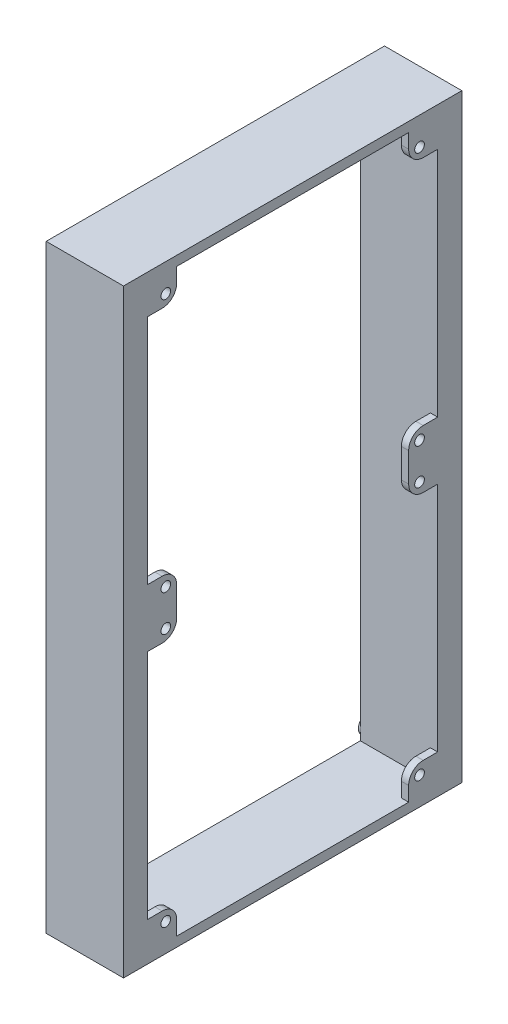
SolidWorks part; units mm, degrees
ref_plane "Front Plane" through (0, 0, 0) normal (1, 0, 0) x (0, 1, 0)
ref_plane "Top Plane" through (0, 0, 0) normal (0, 0, 1) x (0, 1, 0)
ref_plane "Right Plane" through (0, 0, 0) normal (0, 1, 0) x (-1, 0, 0)
sketch "Sketch1" plane through (0, 0, 0) normal (1, 0, 0) x (0, 1, 0)
  line L0 (0, 60) -> (0, -60) construction
  line L1 (-120, -60) -> (120, -60)
  line L2 (-120, -60) -> (-120, 60)
  line L3 (-120, 60) -> (120, 60)
  line L4 (120, -60) -> (120, 60)
  line L5 (-120, -60) -> (120, 60) construction
  line L6 (-120, 60) -> (120, -60) construction
  line L7 (0, 60) -> (0, -60.0055) construction
  line L8 (-120, -60) -> (0, 60) construction
  line L9 (-12, 60) -> (0, 60)
  line L10 (-120, 48) -> (-114, 48)
  line L11 (-120, 48) -> (-120, 60)
  line L12 (-120, 60) -> (-108, 60)
  line L13 (-108, 54) -> (-108, 60)
  line L14 (-12, 60) -> (-12, 54)
  line L15 (-6, 48) -> (0, 48)
  line L16 (0, 60) -> (0, 48)
  line L17 (0, -48) -> (0, -60)
  line L18 (0, -48) -> (-6, -48)
  line L19 (-12, -54) -> (-12, -60)
  line L20 (0, -60) -> (-12, -60)
  line L21 (-108, -60) -> (-120, -60)
  line L22 (-108, -60) -> (-108, -54)
  line L23 (-114, -48) -> (-120, -48)
  line L24 (-120, -60) -> (-120, -48)
  line L25 (0, 48) -> (0, 60)
  line L26 (0, 48) -> (6, 48)
  line L27 (12, 54) -> (12, 60)
  line L28 (0, 60) -> (12, 60)
  line L29 (12, -60) -> (0, -60)
  line L30 (0, -60) -> (0, -48)
  line L31 (6, -48) -> (0, -48)
  line L32 (12, -60) -> (12, -54)
  line L33 (120, -48) -> (120, -60)
  line L34 (120, -60) -> (108, -60)
  line L35 (108, -54) -> (108, -60)
  line L36 (120, -48) -> (114, -48)
  line L37 (108, 60) -> (120, 60)
  line L38 (120, 60) -> (120, 48)
  line L39 (114, 48) -> (120, 48)
  line L40 (108, 60) -> (108, 54)
  line L59 (-124, 70) -> (124, 70)
  line L60 (-124, 70) -> (-124, -70)
  line L61 (-124, -70) -> (124, -70)
  line L62 (124, 70) -> (124, -70)
  line L63 (-124, 70) -> (124, -70) construction
  line L64 (-124, -70) -> (124, 70) construction
  circle A0 centre (-112.5, 52.5) radius 2
  arc A1 (-114, 48) -> (-108, 54) centre (-114, 54) ccw
  arc A2 (-12, 54) -> (-6, 48) centre (-6, 54) ccw
  circle A3 centre (-7.5, 52.5) radius 2
  arc A4 (-6, -48) -> (-12, -54) centre (-6, -54) ccw
  circle A5 centre (-7.5, -52.5) radius 2
  arc A6 (-108, -54) -> (-114, -48) centre (-114, -54) ccw
  circle A7 centre (-112.5, -52.5) radius 2
  arc A8 (6, 48) -> (12, 54) centre (6, 54) ccw
  circle A9 centre (7.5, 52.5) radius 2
  circle A10 centre (7.5, -52.5) radius 2
  arc A11 (12, -54) -> (6, -48) centre (6, -54) ccw
  arc A12 (114, -48) -> (108, -54) centre (114, -54) ccw
  circle A13 centre (112.5, -52.5) radius 2
  arc A14 (108, 54) -> (114, 48) centre (114, 54) ccw
  circle A15 centre (112.5, 52.5) radius 2
  point P0 (0, 0)
  point P12 (0, 0)
  point P16 (-60, 0)
  point P18 (-117, 48)
  point P19 (-108, 57)
  point P22 (-108, 48)
  point P24 (0, 0)
  dimension "D3" = 4
  dimension "D5" = 105
  dimension "D8" = 6
  dimension "D1" = 240
  dimension "D2" = 120
  dimension "D4" = 7.5
  dimension "D6" = 120
  dimension "D7" = 12
  dimension "D9" = 120
  dimension "D10" = 4
  dimension "D11" = 2
  dimension "D12" = 248
  dimension "D13" = 140
extrude "Boss-Extrude2" add sketch "Sketch1" along normal blind 3 contours L10 A1 L13 L3 L2 A0 | L62 L59 L60 L61 L4 L1 L2 L3 | L14 A2 L15 L16 L3 A3 | L26 A8 L27 L3 L16 A9 | L40 A14 L39 L4 L3 A15 | L36 A12 L35 L1 L4 A13 | L32 A11 L31 L17 L1 A10 | L18 A4 L19 L1 L17 A5 | L22 A6 L23 L2 L1 A7 region at (0, -114.4434, -54.4434) region at (0, -5.5566, -54.4434) region at (0, -114.4434, 54.4434) region at (0, 5.5566, -54.4434) region at (0, 114.4434, -54.4434) region at (0, -5.5566, 54.4434) region at (0, 5.5566, 54.4434) region at (0, 114.4434, 54.4434) region at (0, 0, 67.1521)
extrude "Boss-Extrude5" add sketch "Sketch1<6>" against normal blind 29 contours L62 L59 L60 L61 L4 L1 L2 L3 region at (0, 0, 67.1521)
sketch "Sketch1<6>" plane through (0, 0, 0) normal (1, 0, 0) x (0, 1, 0) same geometry as "Sketch1"
sketch "Sketch14" plane through (-29, 0, 0) normal (-1, 0, 0) x (0, -1, 0)
  line L1 (0, 0) -> (-50000, 0) construction
  line L2 (-124, 70) -> (-124, -70) construction
  line L3 (0, 0) -> (0, -50000) construction
  line L4 (120, -60) -> (-120, -60) construction
  line L5 (124, 70) -> (-124, 70) construction
  line L6 (-123, 69) -> (123, 69)
  line L7 (-123, 69) -> (-123, -69)
  line L8 (-123, -69) -> (123, -69)
  line L9 (123, 69) -> (123, -69)
  line L10 (-122.6, 68.6) -> (122.6, 68.6)
  line L11 (122.6, 68.6) -> (122.6, -68.6)
  line L12 (-122.6, -68.6) -> (122.6, -68.6)
  line L13 (-122.6, 68.6) -> (-122.6, -68.6)
  line L14 (124, 70) -> (124, -70) construction
  line L15 (124, -70) -> (-124, -70) construction
  line L17 (120, 60) -> (-120, 60) construction
  circle A0 centre (-116.0377, 63.95) radius 3.15
  circle A1 centre (-116.0377, 63.95) radius 3.95
  circle A2 centre (116.0377, 63.95) radius 3.15
  circle A3 centre (116.0377, 63.95) radius 3.95
  circle A4 centre (116.0377, -63.95) radius 3.15
  circle A5 centre (116.0377, -63.95) radius 3.95
  circle A6 centre (-116.0377, -63.95) radius 3.95
  circle A7 centre (-116.0377, -63.95) radius 3.15
  point P6 (-120, 60)
  point P13 (-124, 0)
  point P18 (0, -60)
  point P44 (-180, 60)
  point P45 (-120, 60)
  point P47 (0, 0)
  point P48 (-120, 60)
  point P49 (0, 0)
  point P50 (0, 0)
  point P51 (-114.2523, 61.3231)
  point P52 (-120, 60)
  point P54 (-114.6335, 66.4975)
  dimension "D1" = 6.3
  dimension "D8" = 3.95
  dimension "D3" = 1
  dimension "D4" = 0.4
  dimension "D5" = 1
  dimension "D6" = 1
  dimension "D7" = 1
  dimension "D2" = 0.8
extrude "Boss-Extrude7" add sketch "Sketch14" along normal blind 0.2 contours L7 L8 L9 L6 | L13 L12 L11 L10
extrude "Boss-Extrude9" add sketch "Sketch14<4>" along normal blind 0.8 contours A1 | A3 | A5 | A6
sketch "Sketch14<4>" plane through (-29, 0, 0) normal (-1, 0, 0) x (0, -1, 0) same geometry as "Sketch14"
extrude "Mounting magnet holes" cut sketch "Sketch14<5>" along normal blind 0.6 and the other way blind 1.5 contours A0 | A7 | A4 | A2
sketch "Sketch14<5>" plane through (-29, 0, 0) normal (-1, 0, 0) x (0, -1, 0) same geometry as "Sketch14"
sketch "Sketch17" plane through (-29.2, 0, 0) normal (-1, 0, 0) x (0, -1, 0)
  line L10 (-122.6, 68.6) -> (122.6, 68.6)
  line L11 (-122.6, 68.6) -> (-122.6, -68.6)
  line L12 (123.2, 69.2) -> (-123.2, 69.2)
  line L13 (-123.2, 69.2) -> (-123.2, -69.2)
  line L14 (-123.2, -69.2) -> (123.2, -69.2)
  line L15 (123.2, -69.2) -> (123.2, 69.2)
  line L16 (123.2, 69.2) -> (-123.2, 69.2)
  line L17 (-123.2, 69.2) -> (-123.2, -69.2)
  line L18 (-123.2, -69.2) -> (123.2, -69.2)
  line L19 (123.2, -69.2) -> (123.2, 69.2)
  line L20 (-122.6, -68.6) -> (122.6, -68.6)
  line L21 (122.6, 68.6) -> (122.6, -68.6)
  dimension "D1" = 0.2
extrude "Boss-Extrude10" add sketch "Sketch17" along normal blind 0.4
chamfer "Chamfer1" distance 0.4 angle 30 4 edges at (-29.6, 0, -69.2) (-29.6, -123.2, 0) (-29.6, 123.2, 0) (-29.6, 0, 69.2) first distance on face at (-29.4, 0, -69.2) first distance on face at (-29.4, -123.2, 0) first distance on face at (-29.4, 123.2, 0) first distance on face at (-29.4, 0, 69.2)
sketch "Sketch18" plane through (3, 0, 0) normal (1, 0, 0) x (0, 1, 0)
  line L0 (-124, 70) -> (124, 70) construction
  line L1 (-124, 70) -> (-124, -70) construction
  line L2 (0, 0) -> (-358.4227, 0) construction
  line L3 (0, 0) -> (0, 85.8788) construction
  circle A0 centre (-119, 65) radius 3.15
  circle A2 centre (119, 65) radius 3.15
  circle A4 centre (119, -65) radius 3.15
  circle A7 centre (-119, -65) radius 3.15
  dimension "D1" = 6.3
  dimension "D2" = 5
  dimension "D3" = 5
  dimension "D4" = 6.3
extrude "Cover magnet holes" cut sketch "Sketch18" against normal blind 2.1 from offset 0.4 offset against normal yes
